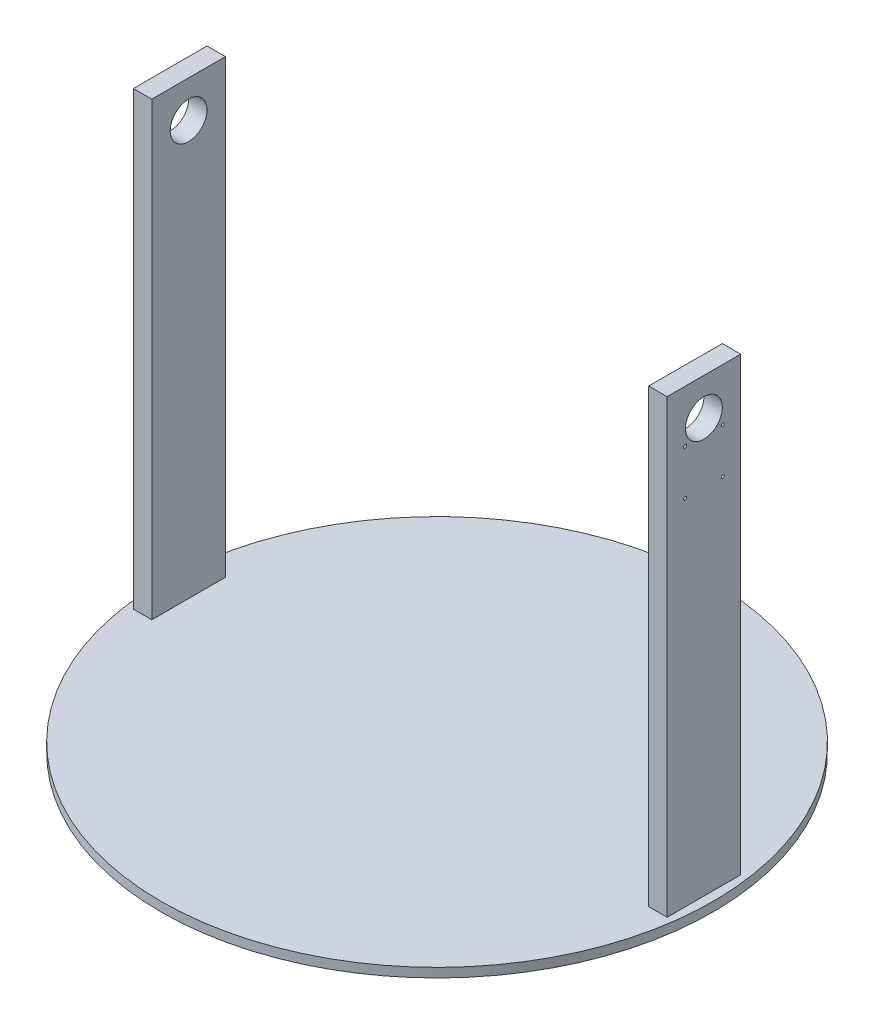
SolidWorks part; units mm, degrees
ref_plane "Front Plane" through (0, 0, 0) normal (0, 0, 1) x (1, 0, 0)
ref_plane "Top Plane" through (0, 0, 0) normal (0, 1, 0) x (1, 0, 0)
ref_plane "Right Plane" through (0, 0, 0) normal (1, 0, 0) x (0, 0, -1)
sketch "Szkic1" plane through (0, 0, 0) normal (0, 1, 0) x (1, 0, 0)
  line L0 (0, 0) -> (140, 0)
  line L1 (140, 0) -> (140, -20)
  line L2 (140, -20) -> (140, 20)
  line L3 (0, 0) -> (-140, 0)
  line L4 (-140, 0) -> (-140, -20)
  line L5 (-140, -20) -> (-140, 20)
  line L7 (145, 20) -> (135, 20)
  line L8 (145, 20) -> (145, -20)
  line L9 (145, -20) -> (135, -20)
  line L10 (135, 20) -> (135, -20)
  line L11 (145, 20) -> (135, -20) construction
  line L12 (145, -20) -> (135, 20) construction
  line L13 (-145, 20) -> (-135, 20)
  line L14 (-145, 20) -> (-145, -20)
  line L15 (-145, -20) -> (-135, -20)
  line L16 (-135, 20) -> (-135, -20)
  line L17 (-145, 20) -> (-135, -20) construction
  line L18 (-145, -20) -> (-135, 20) construction
  circle A0 centre (0, 0) radius 150
  dimension "D1" = 140
  dimension "D9" = 300
  dimension "D2" = 40
  dimension "D3" = 20
  dimension "D4" = 140
  dimension "D5" = 40
  dimension "D6" = 20
  dimension "D7" = 10
  dimension "D8" = 10
extrude "Dodanie-wyciągnięcie1" add sketch "Szkic1" along normal blind 250 contours L16 L15 L14 L13 | L8 L9 L10 L7
extrude "Dodanie-wyciągnięcie2" add sketch "Szkic1<3>" along normal blind 5 contours A0 L13 L16 L10 L7 L8 L9 L15 L14 region at (-145.7574, 0, 0)
sketch "Szkic1<3>" plane through (0, 0, 0) normal (0, 1, 0) x (1, 0, 0) same geometry as "Szkic1"
sketch "Szkic2" plane through (145, 0, 0) normal (1, 0, 0) x (0, 0, -1)
  line L0 (-150, 5) -> (150, 5)
  line L3 (20, 250) -> (20, 5) construction
  line L4 (-20, 250) -> (20, 250) construction
  line L5 (20, 250) -> (20, 210) construction
  circle A0 centre (0, 230) radius 10
  dimension "D3" = 20
  dimension "D1" = 245
  dimension "D2" = 40
extrude "Wytnij-wyciągnięcie1" cut sketch "Szkic2" against normal blind 290 contours A0 region at (145, 230, 0)
sketch "Szkic3" plane through (145, 0, 0) normal (1, 0, 0) x (0, 0, -1)
  line L0 (-20, 250) -> (20, 250) construction
  line L1 (0, 240) -> (0, 250) construction
  line L2 (0, 240) -> (0, 220) construction
  line L3 (0, 230) -> (0, 194.89) construction
  line L4 (12.36, 194.89) -> (-12.36, 194.89)
  line L5 (-12.36, 194.89) -> (-12.36, 192.89)
  line L6 (-12.36, 192.89) -> (12.36, 192.89)
  line L7 (12.36, 192.89) -> (12.36, 194.89)
  line L8 (-12.36, 194.89) -> (-12.36, 221.7)
  line L9 (12.36, 194.89) -> (12.36, 221.7)
  line L10 (-12.36, 221.7) -> (12.36, 221.7) construction
  line L11 (10.25, 221.7) -> (-10.25, 221.7)
  line L12 (-10.25, 221.7) -> (-10.25, 197.25)
  line L13 (10.25, 221.7) -> (10.25, 197.25)
  circle A0 centre (0, 230) radius 10 construction
  circle A1 centre (-10.25, 221.7) radius 0.8
  circle A2 centre (10.25, 221.7) radius 0.8
  circle A3 centre (-10.25, 197.25) radius 0.8
  circle A4 centre (10.25, 197.25) radius 0.8
  point P16 (0, 194.89)
  point P23 (0, 221.7)
  dimension "D1" = 10
  dimension "D8" = 1.6
  dimension "D9" = 1.6
  dimension "D11" = 1.6
  dimension "D12" = 1.6
  dimension "D2" = 20
  dimension "D3" = 35.11
  dimension "D4" = 24.72
  dimension "D5" = 2
  dimension "D6" = 26.81
  dimension "D7" = 20.5
  dimension "D10" = 24.45
extrude "Wytnij-wyciągnięcie4" cut sketch "Szkic3" against normal blind 10 contours A3 | A4 | A2 | A1 region at (145, 197.7997, -10.7997) region at (145, 197.7997, 9.7003)
